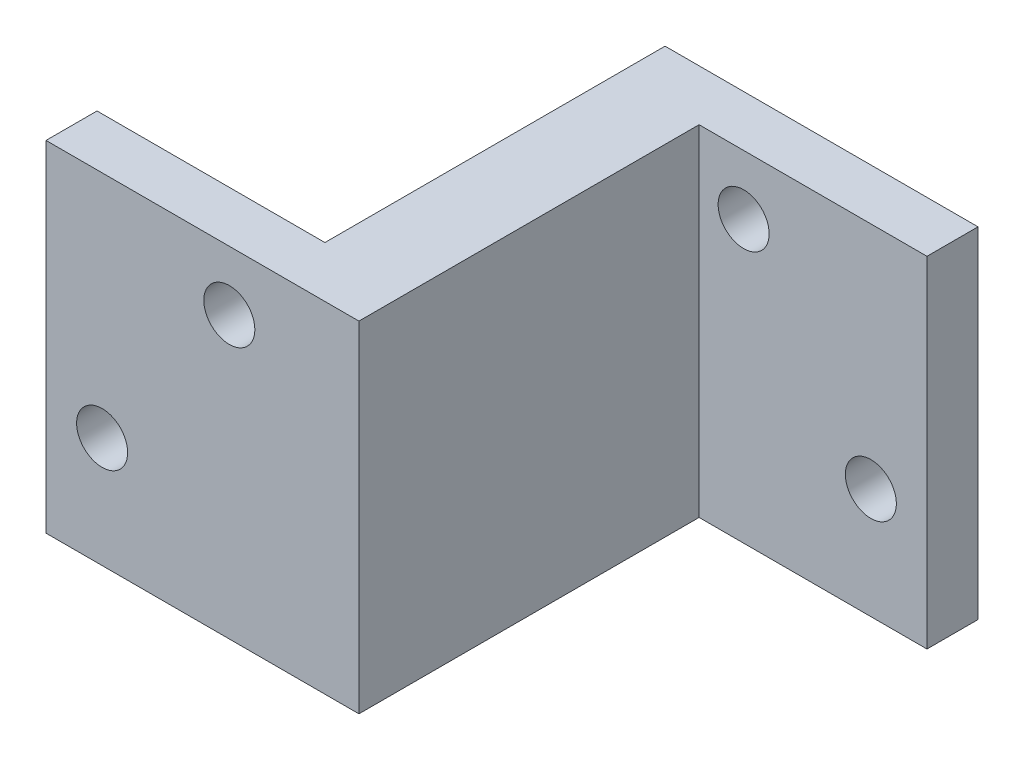
SolidWorks part; units mm, degrees
ref_plane "Front Plane" through (0, 0, 0) normal (0, 0, 1) x (1, 0, 0)
ref_plane "Top Plane" through (0, 0, 0) normal (0, 1, 0) x (1, 0, 0)
ref_plane "Right Plane" through (0, 0, 0) normal (1, 0, 0) x (0, 0, -1)
sketch "Sketch1" plane through (0, 0, 0) normal (0, 1, 0) x (1, 0, 0)
  line L0 (0, 0) -> (18.4, 0)
  line L1 (18.4, 0) -> (18.4, 20)
  line L2 (18.4, 20) -> (31.8, 20)
  line L3 (31.8, 20) -> (31.8, 23)
  line L4 (31.8, 23) -> (13.4, 23)
  line L5 (13.4, 23) -> (13.4, 3)
  line L6 (13.4, 3) -> (0, 3)
  line L7 (0, 3) -> (0, 0)
  dimension "D1" = 13.4
  dimension "D2" = 5
  dimension "D3" = 3
  dimension "D4" = 17
extrude "Boss-Extrude1" add sketch "Sketch1" along normal blind 20
sketch "Sketch2" plane through (0, 0, -20) normal (0, 0, 1) x (1, 0, 0)
  line L1 (31.8, 20) -> (31.8, 0) construction
  line L2 (31.8, 0) -> (13.4, 0) construction
  circle A0 centre (28.5, 6.5) radius 1.5
  circle A1 centre (21.02, 16.5) radius 1.5
  dimension "D1" = 3
  dimension "D2" = 6.5
  dimension "D3" = 3.3
  dimension "D4" = 10.78
  dimension "D5" = 16.5
extrude "Cut-Extrude1" cut sketch "Sketch2" against normal through all both and the other way through all
ref_plane "Plane1" through (15.9, 0, 0) normal (-1, 0, 0) x (0, 0, 1)
mirror "Mirror1" about plane through (15.9, 0, 0) normal (-1, 0, 0) of "Cut-Extrude1"
